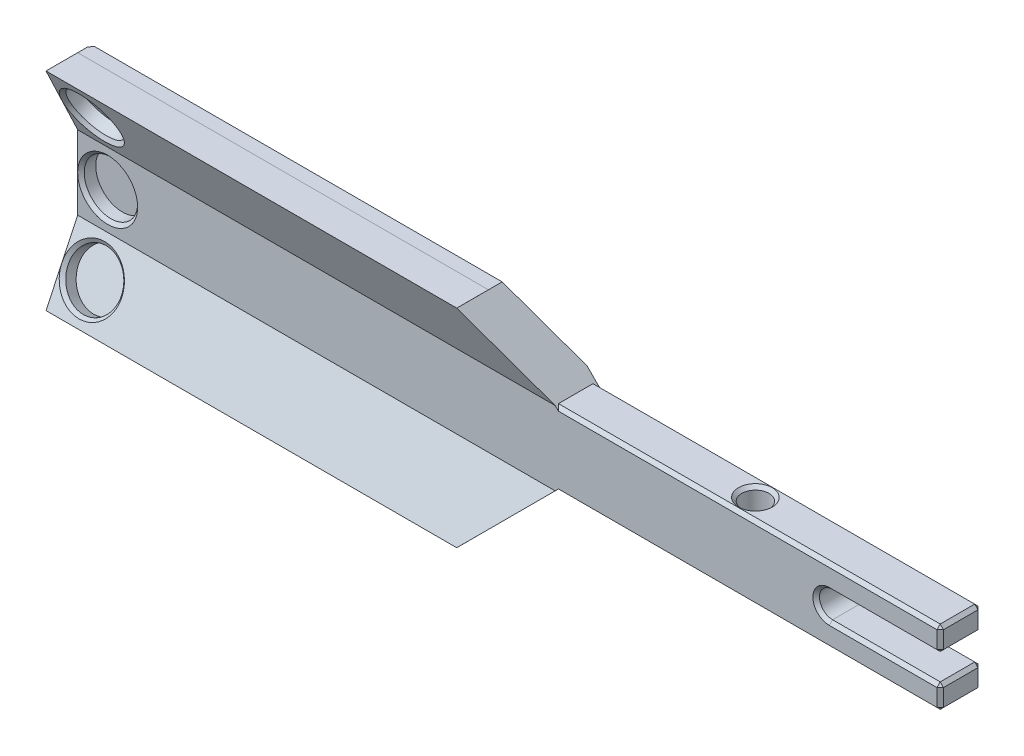
SolidWorks part; units mm, degrees
ref_plane "Front" through (0, 0, 0) normal (0, 0, 1) x (1, 0, 0)
ref_plane "Top" through (0, 0, 0) normal (0, 1, 0) x (1, 0, 0)
ref_plane "Right" through (0, 0, 0) normal (1, 0, 0) x (0, 0, -1)
sketch "Sketch1" plane through (0, 0, 0) normal (0, 0, 1) x (1, 0, 0)
  line L1 (52.5, -4.5) -> (-52.5, -4.5)
  line L2 (52.5, -4.5) -> (52.5, 4.5)
  line L3 (52.5, 4.5) -> (-52.5, 4.5)
  line L4 (-52.5, -4.5) -> (-52.5, 4.5)
  line L5 (52.5, -4.5) -> (-52.5, 4.5) construction
  line L6 (52.5, 4.5) -> (-52.5, -4.5) construction
  point P0 (0, 0)
  dimension "D1" = 9
  dimension "D2" = 105
extrude "Boss-Extrude1" add sketch "Sketch1" along normal blind 5
sketch "Sketch2" plane through (0, 4.5, 0) normal (0, 1, 0) x (1, 0, 0)
  line L0 (52.5, -5) -> (52.5, 0) construction
  line L2 (52.5, 0) -> (-52.5, 0) construction
  circle A0 centre (27.5, -2.5) radius 1.65
  dimension "D3" = 3.3
  dimension "D1" = 2.5
  dimension "D2" = 25
sketch "Sketch4" plane through (0, 0, 5) normal (0, 0, 1) x (1, 0, 0)
  line L0 (39, 0) -> (45, 0) construction
  line L1 (39, 1.6) -> (45, 1.6)
  line L2 (39, -1.6) -> (45, -1.6)
  arc A0 (39, 1.6) -> (39, -1.6) centre (39, 0) ccw
  arc A1 (45, -1.6) -> (45, 1.6) centre (45, 0) ccw
  point P2 (42, 0)
  dimension "D1" = 1.6
  dimension "D2" = 42
  dimension "D3" = 6
extrude "Cut-Extrude1" cut sketch "Sketch4" against normal blind 5
sketch "Sketch14" plane through (0, 0, 5) normal (0, 0, 1) x (1, 0, 0)
  line L0 (39, -1.6) -> (45, -1.6) construction
  line L1 (44.5, -1.6) -> (52.5, -1.6)
  line L2 (44.5, -1.6) -> (44.5, 1.6)
  line L3 (44.5, 1.6) -> (52.5, 1.6)
  line L4 (52.5, -1.6) -> (52.5, 1.6)
  line L5 (52.5, -4.5) -> (52.5, 4.5) construction
  line L6 (45, 1.6) -> (39, 1.6) construction
  dimension "D1" = 8
extrude "Cut-Extrude7" cut sketch "Sketch14" against normal blind 10
sketch "Sketch8" plane through (0, 0, 0) normal (0, 0, -1) x (-1, 0, 0)
  line L0 (52.5, 4.5) -> (52.5, -4.5) construction
  line L1 (52.5, 12.63) -> (2.5, 12.63)
  line L2 (52.5, 12.63) -> (52.5, -12.63)
  line L3 (52.5, -12.63) -> (2.5, -12.63)
  line L4 (2.5, 12.63) -> (2.5, -12.63)
  line L6 (-52.5, 4.5) -> (52.5, 4.5) construction
  dimension "D1" = 25.26
  dimension "D2" = 8.13
  dimension "D3" = 50
extrude "Boss-Extrude3" add sketch "Sketch8" against normal up to surface (5 mm away) up to face at (22.675, 0, 5)
sketch "Sketch9" plane through (-52.5, 0, 0) normal (-1, 0, 0) x (0, 0, 1)
  line L0 (5, 12.63) -> (5, -12.63) construction
  line L1 (5, 12.6327) -> (8.8548, 12.6327)
  line L2 (8.8548, 12.6327) -> (5, 4.5)
  line L3 (5, 4.5) -> (5, 12.6327)
  line L4 (-3.9634, 0) -> (12.9509, 0) construction
  line L5 (8.8548, -12.6327) -> (5, -4.5)
  line L6 (5, -12.6327) -> (8.8548, -12.6327)
  line L7 (5, -4.5) -> (5, -12.6327)
  circle A0 centre (25, 0) radius 20 construction
  dimension "D1" = 40
  dimension "D2" = 9
  dimension "D3" = 9
extrude "Boss-Extrude4" add sketch "Sketch9" against normal up to surface (50 mm away) up to face at (-2.5, 8.565, 2.5)
sketch "Sketch13" plane through (-52.5, 0, 0) normal (-1, 0, 0) x (0, 0, 1)
  line L0 (0, 5.625) -> (3.3203, 12.63)
  line L1 (0, 12.63) -> (0, -12.63) construction
  line L2 (5, 12.63) -> (0, 12.63) construction
  line L3 (3.3203, 12.63) -> (-2, 12.63)
  line L4 (-2, 12.63) -> (-2, -12.63)
  line L5 (-2, -12.63) -> (3.3203, -12.63)
  line L6 (5, -12.63) -> (0, -12.63) construction
  line L7 (3.3203, -12.63) -> (0, -5.625)
  line L8 (0, -5.625) -> (0, 5.625)
  line L10 (5, 4.5) -> (8.8548, 12.6327) construction
  line L11 (8.8548, -12.6327) -> (5, -4.5) construction
  dimension "D1" = 5
  dimension "D2" = 5
  dimension "D3" = 2
extrude "Cut-Extrude6" cut sketch "Sketch13" against normal through all
chamfer "Chamfer4" distance 8.13 2 edges at (-2.5, 4.5, 2.5) (-2.5, -4.5, 2.5)
sketch "Sketch10" plane through (-52.5, 0, 0) normal (-1, 0, 0) x (0, 0, 1)
  line L0 (5, 4.5) -> (5, -4.5) construction
  line L1 (5, 4.5) -> (8.8548, 12.6327) construction
  line L2 (8.8548, -12.6327) -> (5, -4.5) construction
  circle A0 centre (25, 0) radius 20
sketch "Sketch11" plane through (0, 0, 5) normal (0, 0, 1) x (1, 0, 0)
  line L2 (-52.5, 4.5) -> (-52.5, -4.5) construction
  circle A0 centre (-48.85, 0) radius 3.25
  dimension "D1" = 6.5
  dimension "D2" = 3.65
extrude "Cut-Extrude3" cut sketch "Sketch11" against normal blind 1.8
sketch "Sketch12" plane through (0, -1.1096, 2.341) normal (0, -0.4283, 0.9036) x (1, 0, 0)
  line L1 (-2.5, 15.2079) -> (-52.5, 15.2079) construction
  line L2 (-52.5, 30.7079) -> (-52.5, -9.2921) construction
  circle A0 centre (-48.85, 10.7079) radius 3.25
  dimension "D1" = 6.5
  dimension "D2" = 4.5
  dimension "D3" = 3.65
extrude "Cut-Extrude4" cut sketch "Sketch12" against normal blind 1.8
mirror "Mirror2" about plane through (0, 0, 0) normal (0, 1, 0) of "Cut-Extrude4"
chamfer "Chamfer2" distance 0.4 angle 45 3 edges at (-45.6, 0, 5) (-48.85, -5.6295, 5.5354) (-48.85, 5.6295, 5.5354)
ref_plane "Plane1" through (-48.5, 0, 0) normal (-1, 0, 0) x (0, 0, 1)
extrude "Cut-Extrude5" cut sketch "Sketch2" against normal blind 10
chamfer "Chamfer5" distance 0.4 angle 45 20 edges at (25.85, -4.5, 2.5) (25.85, 4.5, 2.5) (52.5, 4.5, 2.5) (29.065, 4.5, 5) (52.5, -3.05, 5) (52.5, 3.05, 5) (29.065, -4.5, 5) (52.5, -4.5, 2.5) (29.065, 4.5, 0) (29.065, -4.5, 0) (52.5, 3.05, 0) (52.5, -3.05, 0) (45.75, -1.6, 0) (37.4, 0, 0) (45.75, 1.6, 0) (45.75, 1.6, 5) (37.4, 0, 5) (45.75, -1.6, 5) (52.5, 1.6, 2.5) (52.5, -1.6, 2.5)
chamfer "Chamfer6" distance 0.4 angle 45 3 edges at (-52.5, 9.1275, 1.6602) (-52.5, -9.1275, 1.6602) (-52.5, 0, 0)
